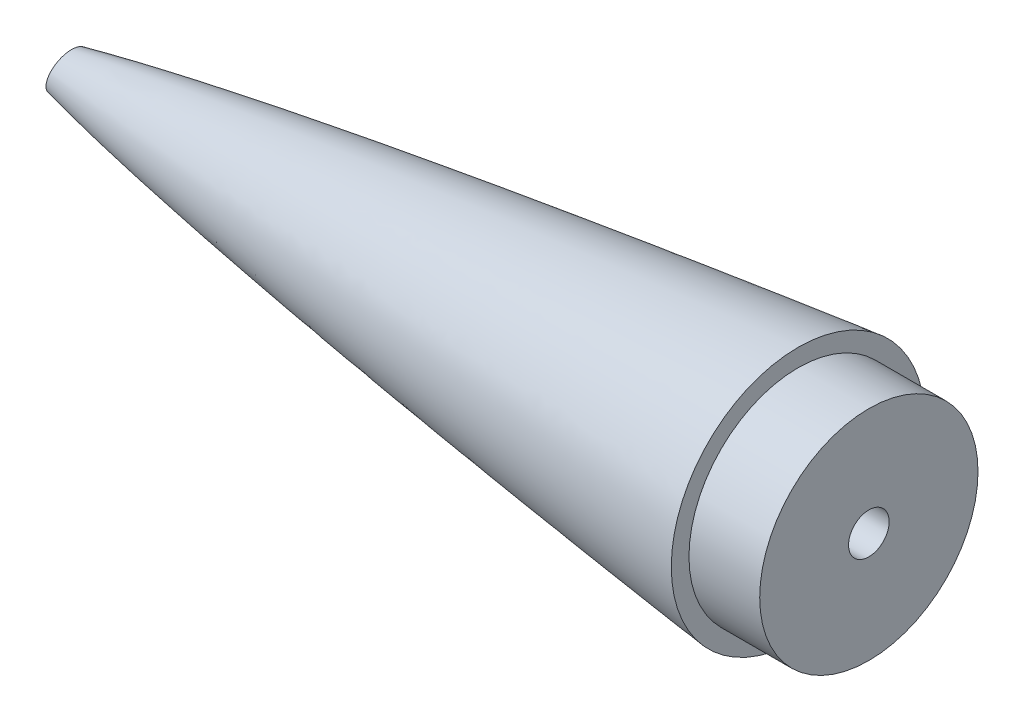
SolidWorks part; units mm, degrees
ref_plane "Front Plane" through (0, 0, 0) normal (0, 0, 1) x (1, 0, 0)
ref_plane "Top Plane" through (0, 0, 0) normal (0, 1, 0) x (1, 0, 0)
ref_plane "Right Plane" through (0, 0, 0) normal (1, 0, 0) x (0, 0, -1)
sketch "Sketch1" plane through (0, 0, 0) normal (0, 0, 1) x (1, 0, 0)
  line L6 (0.0514, -0.1338) -> (109.3782, -0.1338)
  line L8 (100.4882, 13.5822) -> (109.3782, 13.5822)
  line L9 (109.3782, 13.5822) -> (109.3782, -0.1338)
  line L10 (100.4882, 15.8047) -> (100.4882, 13.5822)
  spline S5 degree 4 poles (0.0514, -0.1338) (0.0552, -0.1267) (0.0638, -0.1134) (0.0864, -0.0909) (0.124, -0.0613) (0.1696, -0.0296) (0.2373, 0.0121) (0.3206, 0.0586) (0.444, 0.1217) (0.609, 0.1982) (0.8023, 0.2808) (1.0241, 0.3689) (1.2674, 0.4603) (1.5321, 0.5547) (1.9669, 0.7026) (2.7462, 0.9493) (4.169, 1.3583) (6.8533, 2.0434) (11.8366, 3.1571) (21.2787, 4.9817) (38.2766, 7.7916) (66.0855, 11.7234) (103.546, 16.2897) (148.3227, 21.1103) (197.0023, 25.8223) (245.7188, 30.1326) (294.4636, 34.1082) (343.2313, 37.7909) (392.0185, 41.2062) (440.8227, 44.3696) (489.642, 47.2884) (538.4754, 49.9634) (587.3218, 52.3879) (636.1808, 54.5467) (678.943, 56.179) (715.6038, 57.3637) (745.2557, 58.1525) (765.2912, 58.5863) (781.8204, 58.8601) (792.2379, 58.9748) (797.4469, 59.0114) (800.0514, 59.0162) knots 0 0 0 0 0 0.00004 0.000079 0.000158 0.000237 0.000317 0.000475 0.000633 0.000928 0.001222 0.001522 0.001822 0.002222 0.002622 0.00381 0.005894 0.009596 0.016421 0.029243 0.053793 0.095411 0.156318 0.217224 0.278131 0.339037 0.399944 0.46085 0.521757 0.582663 0.64357 0.704476 0.765383 0.826289 0.887196 0.917649 0.948102 0.974051 0.987026 1 1 1 1 1 construction
  spline S6 degree 4 poles (0.0514, -0.1338) (0.0552, -0.1267) (0.0638, -0.1134) (0.0864, -0.0909) (0.124, -0.0613) (0.1696, -0.0296) (0.2373, 0.0121) (0.3206, 0.0586) (0.444, 0.1217) (0.609, 0.1982) (0.8023, 0.2808) (1.0241, 0.3689) (1.2674, 0.4603) (1.5321, 0.5547) (1.9669, 0.7026) (2.7462, 0.9493) (4.169, 1.3583) (6.8533, 2.0434) (11.8366, 3.1571) (21.2787, 4.9817) (38.2766, 7.7916) (60.2248, 10.8948) (79.6614, 13.3517) (94.222, 15.0794) (100.4882, 15.8047) knots 0 0 0 0 0 0.00004 0.000079 0.000158 0.000237 0.000317 0.000475 0.000633 0.000928 0.001222 0.001522 0.001822 0.002222 0.002622 0.00381 0.005894 0.009596 0.016421 0.029243 0.053793 0.095411 0.126835 0.126835 0.126835 0.126835 0.126835
  dimension "D1" = 109.3268
  dimension "D3" = 13.716
  dimension "D4" = 8.89
  dimension "D2" = 15.9385
revolve "Revolve1" add sketch "Sketch1" angle 360 about L6 region at (68.6451, 5.6151, 0)
hole_wizard "1/4-20 Tapped Hole1" positions "Sketch4" profile "Sketch6" tap size "1/4-20" standard "ANSI Inch" end condition through all
sketch "Sketch4" plane through (109.3782, 0, 0) normal (1, 0, 0) x (0, 0, -1)
  point P0 (0, 0)
cosmetic thread "Hole Thread1" parameters "D2"=6.35
sketch "Sketch6" plane through (109.3782, 0, 0) normal (0, 1, 0) x (0, 0, -1)
  line L0 (0, 0) -> (0, 109.3268)
  line L1 (0, 109.3268) -> (2.5527, 109.3268)
  line L2 (2.5527, 109.3268) -> (2.5527, 0)
  line L5 (2.5527, 0) -> (0, 0)
  line L11 (0, -6.35) -> (0, 107.95) construction
  dimension "Thru Tap Drill Dia." = 5.1054
  dimension "Thru Tap Drill Depth" = 109.3268
